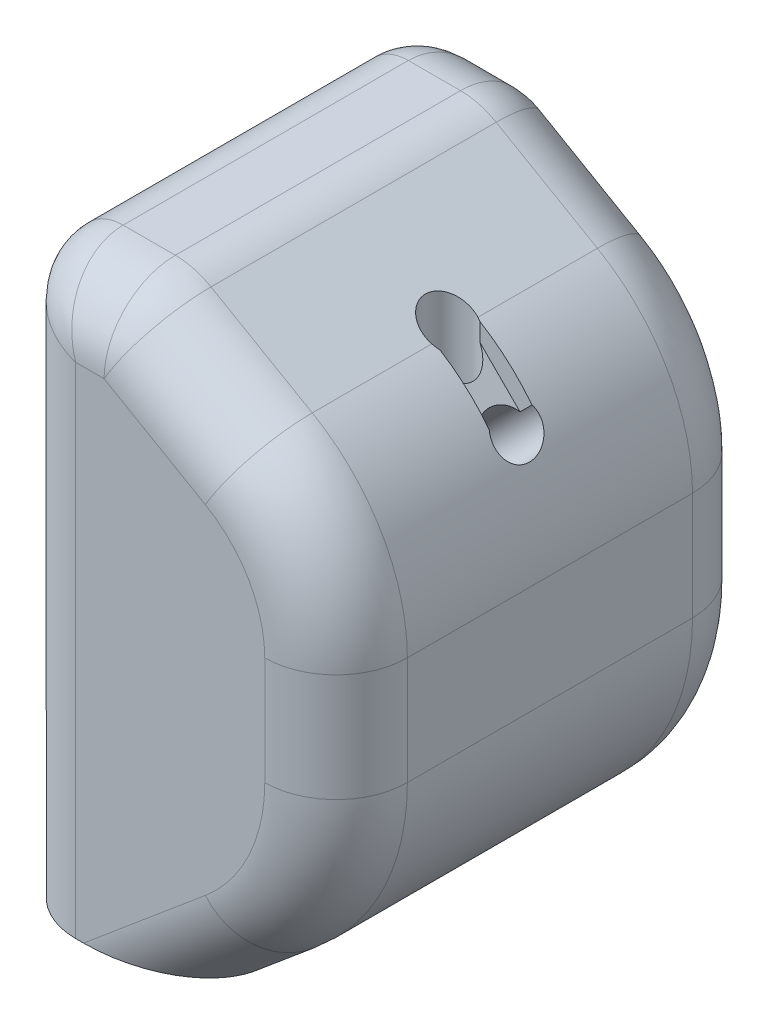
SolidWorks part; units mm, degrees
ref_plane "Front Plane" through (0, 0, 0) normal (0, 0, 1) x (1, 0, 0)
ref_plane "Top Plane" through (0, 0, 0) normal (0, 1, 0) x (1, 0, 0)
ref_plane "Right Plane" through (0, 0, 0) normal (1, 0, 0) x (0, 0, -1)
sketch "Sketch1" plane through (0, 0, 0) normal (0, 0, 1) x (1, 0, 0)
  line L0 (0, 0) -> (8, 0)
  line L1 (8, 0) -> (10.3866, 2.0026)
  line L2 (0, 0) -> (0, 22)
  line L3 (2, 24) -> (4.1962, 24)
  line L4 (5.6962, 23.5981) -> (9.9588, 21.1371)
  line L5 (13.9588, 14.2089) -> (13.9588, 9.6631)
  arc A0 (0, 22) -> (2, 24) centre (2, 22) cw
  arc A1 (5.6962, 23.5981) -> (4.1962, 24) centre (4.1962, 21) ccw
  arc A2 (13.9588, 14.2089) -> (9.9588, 21.1371) centre (5.9588, 14.2089) ccw
  arc A3 (13.9588, 9.6631) -> (10.3866, 2.0026) centre (3.9588, 9.6631) cw
  point P9 (0, 24)
  point P12 (5, 24)
  point P15 (13.9588, 18.8277)
  point P18 (13.9588, 5)
  dimension "D7" = 2
  dimension "D8" = 3
  dimension "D9" = 8
  dimension "D10" = 10
  dimension "D1" = 8
  dimension "D2" = 140
  dimension "D3" = 5
  dimension "D4" = 24
  dimension "D5" = 5
  dimension "D6" = 150
extrude "Boss-Extrude1" add sketch "Sketch1" along normal blind 18
sketch "Sketch2" plane through (0, 0, 0) normal (0, 0, -1) x (-1, 0, 0)
  line L0 (0, 0) -> (-8, 0) construction
  line L2 (-6, 0) -> (-4, 0)
  line L3 (-6, 0) -> (-6, 1.2087)
  line L5 (-4, 0) -> (-4, 1.2087)
  arc A0 (-4, 1.2087) -> (-6, 1.2087) centre (-5, 3.5) ccw
  point P0 (-5, 0)
  dimension "D2" = 5
  dimension "D1" = 5
  dimension "D3" = 3.5
  dimension "D4" = 2
  dimension "D5" = 1
extrude "Cut-Extrude1" cut sketch "Sketch2" against normal blind 13 from offset 2.5 offset against normal yes
sketch "Sketch4" plane through (0, 0, 0) normal (0, 1, 0) x (1, 0, 0)
  circle A0 centre (9.7202, -9) radius 1
  dimension "D1" = 2
  dimension "D2" = 9.7202
  dimension "D3" = 9
extrude "Cut-Extrude3" cut sketch "Sketch4" along normal blind 25
ref_plane "Plane1" through (15.5479, 15.5479, 0) normal (0.7071, 0.7071, 0) x (0, 0, -1)
sketch "Sketch5" plane through (15.5479, 15.5479, 0) normal (0.7071, 0.7071, 0) x (0, 0, -1)
  circle A0 centre (-8.9711, 4.4042) radius 1
  point P0 (-8.9711, 7.9042)
  dimension "D1" = 2
  dimension "D2" = 3.5
  dimension "D3" = 1
extrude "Cut-Extrude4" cut sketch "Sketch5" against normal blind 4 and the other way blind 2
fillet "Fillet1" radius 3 18 edges at (9.1933, 1.0013, 0) (13.0218, 5.4369, 0) (13.9588, 11.936, 0) (12.887, 18.2089, 0) (7.8275, 22.3676, 0) (4.9726, 23.8978, 0) (3.0981, 24, 0) (0.5858, 23.4142, 0) (9.1933, 1.0013, 18) (13.0218, 5.4369, 18) (13.9588, 11.936, 18) (12.887, 18.2089, 18) (7.8275, 22.3676, 18) (4.9726, 23.8978, 18) (3.0981, 24, 18) (0.5858, 23.4142, 18) (0, 11, 0) (0, 11, 18)
sketch "Sketch6" plane through (15.5479, 15.5479, 0) normal (0.7071, 0.7071, 0) x (0, 0, -1)
  line L1 (-9.8711, 4.4042) -> (-8.0711, 4.4042)
  line L2 (-9.8711, 4.4042) -> (-9.8711, 8.1703)
  line L3 (-9.8711, 8.1703) -> (-8.0711, 8.1703)
  line L4 (-8.0711, 4.4042) -> (-8.0711, 8.1703)
  circle A0 centre (-8.9711, 4.4042) radius 1 construction
  ellipse E0 centre (-9, 8.1703) end of major axis (-9, 9.2856) minor radius 1 (-8.0289, 7.9042) -> (-9.9711, 7.9042) ccw construction
  ellipse E1 centre (-9, 8.1703) end of major axis (-9, 9.2856) minor radius 1 (-8.0289, 7.9042) -> (-9.9711, 7.9042) ccw construction
  point P5 (-9.9537, 4.2181)
  point P10 (-8.9711, 4.4042)
  dimension "D1" = 1.8
  dimension "D2" = 0.9
  dimension "D3" = 0.1289
extrude "Cut-Extrude5" cut sketch "Sketch6" along normal blind 1 and the other way blind 0.5
sketch "Sketch7" plane through (0, 0, 0) normal (-1, 0, 0) x (0, 0, 1)
  line L0 (2.9999, 14.4276) -> (3, 12)
  line L1 (3, 22) -> (3, 0) construction
  line L2 (3, 12) -> (15, 12)
  line L3 (15, 0) -> (15, 22) construction
  line L4 (15, 12) -> (15, 14.4276)
  line L5 (15, 22) -> (3, 22) construction
  spline S0 degree 3 poles (2.9999, 14.4276) (2.3845, 21.2849) (9.084, 24.4107) (15.4091, 21.3672) (15, 14.4276) knots 0 0 0 0 0.49958 1 1 1 1
  dimension "D1" = 10
extrude "Cut-Extrude6" cut sketch "Sketch7" against normal blind 0.5
ref_plane "Plane2" through (0, 0, 9) normal (0, 0, 1) x (1, 0, 0)
